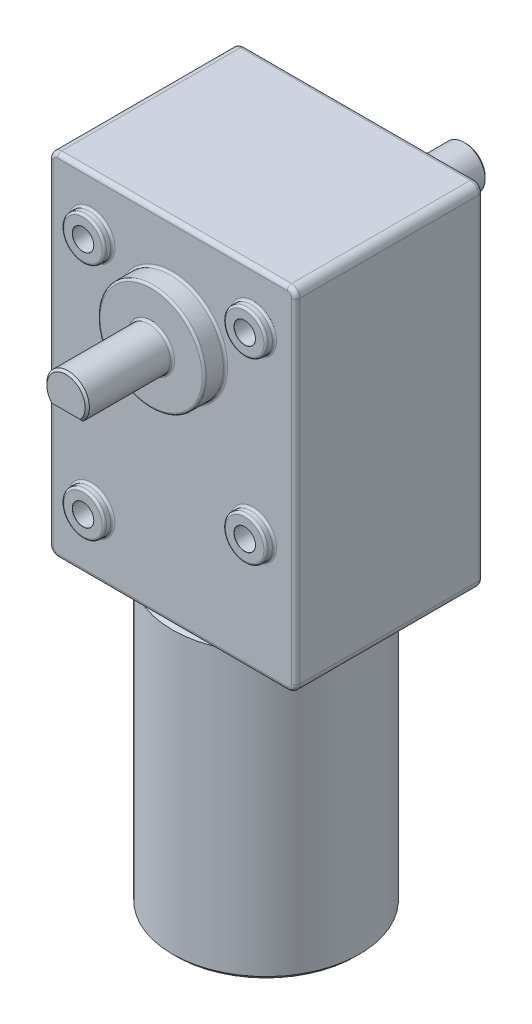
SolidWorks part; units mm, degrees
material "Malleable Cast Iron"
ref_plane "Front Plane" through (0, 0, 0) normal (0, 0, 1) x (1, 0, 0)
ref_plane "Top Plane" through (0, 0, 0) normal (0, 1, 0) x (1, 0, 0)
ref_plane "Right Plane" through (0, 0, 0) normal (1, 0, 0) x (0, 0, -1)
sketch "Sketch1" plane through (0, 0, 0) normal (0, 0, 1) x (1, 0, 0)
  line L0 (0, 0) -> (0, 31499.1926) construction
  line L2 (-29, -41.25) -> (29, -41.25)
  line L3 (-29, -41.25) -> (-29, 41.25)
  line L4 (-29, 41.25) -> (29, 41.25)
  line L5 (29, -41.25) -> (29, 41.25)
  line L6 (-29, -41.25) -> (29, 41.25) construction
  line L7 (-29, 41.25) -> (29, -41.25) construction
  point P3 (0, 0)
  dimension "D1" = 82.5
  dimension "D2" = 58
extrude "Boss-Extrude1" add sketch "Sketch1" along normal mid plane 44 contours L3 L4 L5 L2
sketch "Sketch2" plane through (0, 0, 22) normal (0, 0, 1) x (1, 0, 0)
  line L0 (-29, 41.25) -> (29, 41.25) construction
  circle A0 centre (0, 17.75) radius 12.5
  dimension "D1" = 25
  dimension "D2" = 23.5
extrude "Boss-Extrude2" add sketch "Sketch2" along normal mid plane 54 from surface starting at plane "Front Plane"
sketch "Sketch3" plane through (0, 0, 27) normal (0, 0, 1) x (1, 0, 0)
  circle A0 centre (0, 17.75) radius 5
  circle A1 centre (0, 17.75) radius 12.5 construction
  dimension "D1" = 10
extrude "Boss-Extrude3" add sketch "Sketch3" along normal blind 20
sketch "Sketch4" plane through (0, 0, 0) normal (1, 0, 0) x (0, 0, -1)
  line L0 (-27, 22.75) -> (-47, 22.75) construction
  line L1 (-47, 12.75) -> (-32, 12.75)
  line L2 (-47, 12.75) -> (-47, 14.25)
  line L3 (-47, 14.25) -> (-32, 14.25)
  line L4 (-32, 12.75) -> (-32, 14.25)
  dimension "D1" = 8.5
  dimension "D2" = 15
extrude "Cut-Extrude1" cut sketch "Sketch4" against normal through all both and the other way through all
sketch "Sketch5" plane through (0, 0, 22) normal (0, 0, 1) x (1, 0, 0)
  line L0 (0, 0) -> (0, 50000) construction
  circle A0 centre (-19, 28.75) radius 5
  circle A1 centre (0, 17.75) radius 12.5 construction
  circle A2 centre (0, 17.75) radius 12.5 construction
  circle A3 centre (19, 28.75) radius 5
  circle A4 centre (-19, -27.25) radius 5
  circle A5 centre (19, -13.25) radius 5
  dimension "D1" = 10
  dimension "D2" = 38
  dimension "D3" = 11
  dimension "D4" = 56
  dimension "D5" = 42
extrude "Boss-Extrude4" add sketch "Sketch5" along normal blind 2
hole_wizard "Ø5.0 (5) Diameter Hole1" positions "Sketch8" profile "Sketch9" hole size "Ø5.0" standard "ANSI Metric"
sketch "Sketch8" plane through (0, 0, 24) normal (0, 0, 1) x (1, 0, 0)
  point P2 (19, 28.75)
  point P5 (19, -13.25)
  point P8 (-19, -27.25)
  point P13 (-19, 28.75)
sketch "Sketch9" plane through (19, 28.75, 24) normal (1, 0, 0) x (0, -1, 0)
  line L0 (0, 0) -> (0, 11.5022)
  line L1 (0, 11.5022) -> (2.5, 10)
  line L2 (2.5, 10) -> (2.5, 0.025)
  line L3 (2.5, 0.025) -> (2.525, 0)
  line L5 (2.525, 0) -> (0, 0)
  line L6 (-2.5, 0.025) -> (-2.525, 0) construction
  line L10 (0, 11.5022) -> (-2.5, 10) construction
  line L11 (0, -6.35) -> (0, 107.95) construction
  dimension "Hole Dia." = 5
  dimension "Hole Depth" = 10
  dimension "Near C'Sink Dia." = 5.05
  dimension "Near C'Sink Angle" = 90
  dimension "Drill Angle" = 118
chamfer "Chamfer1" distance 0.5 angle 45 2 edges at (0, 22.75, 47) (0, 14.25, 47)
mirror "Mirror3" about plane through (0, 0, 0) normal (0, 0, 1) of "Boss-Extrude3", "Cut-Extrude1", "Boss-Extrude4", "Ø5.0 (5) Diameter Hole1", "Chamfer1"
fillet "Fillet1" radius 0.5 22 edges at (12.5, 17.75, 27) (5, 17.75, 27) (14, 28.75, 22) (24, -13.25, 22) (-14, -27.25, 22) (-14, 28.75, 22) (12.5, 17.75, 22) (-14, 28.75, -22) (-14, 28.75, -24) (-14, -27.25, -22) (-14, -27.25, -24) (24, -13.25, -22) (24, -13.25, -24) (14, 28.75, -22) (14, 28.75, -24) (12.5, 17.75, -22) (12.5, 17.75, -27) (5, 17.75, -27) (-14, 28.75, 24) (14, 28.75, 24) (-14, -27.25, 24) (24, -13.25, 24)
fillet "Fillet3" radius 1 8 edges at (0, -41.25, 22) (-29, 0, 22) (0, 41.25, 22) (29, 0, 22) (29, 0, -22) (0, 41.25, -22) (-29, 0, -22) (0, -41.25, -22)
fillet "Fillet4" radius 2 13 edges at (28.7071, -40.9571, 21.7071) (28.7071, -40.9571, -21.7071) (-28.7071, -40.9571, 21.7071) (-28.7071, -40.9571, -21.7071) (-28.7071, 40.9571, 21.7071) (-28.7071, 40.9571, -21.7071) (28.7071, 40.9571, 21.7071) (28.7071, 40.9571, -21.7071) (29, -41.25, 0) (-29, -41.25, 0) (-29, 41.25, 0) (29, 41.25, 0) (16.5, 28.75, -14)
sketch "Sketch10" plane through (0, -41.25, 0) normal (0, -1, 0) x (1, 0, 0)
  circle A0 centre (0, 0) radius 22
  dimension "D1" = 44
extrude "Boss-Extrude5" add sketch "Sketch10" along normal blind 68 separate body
chamfer "Chamfer2" distance 1 angle 45 2 edges at (0, -41.25, -22) (0, -109.25, -22)
